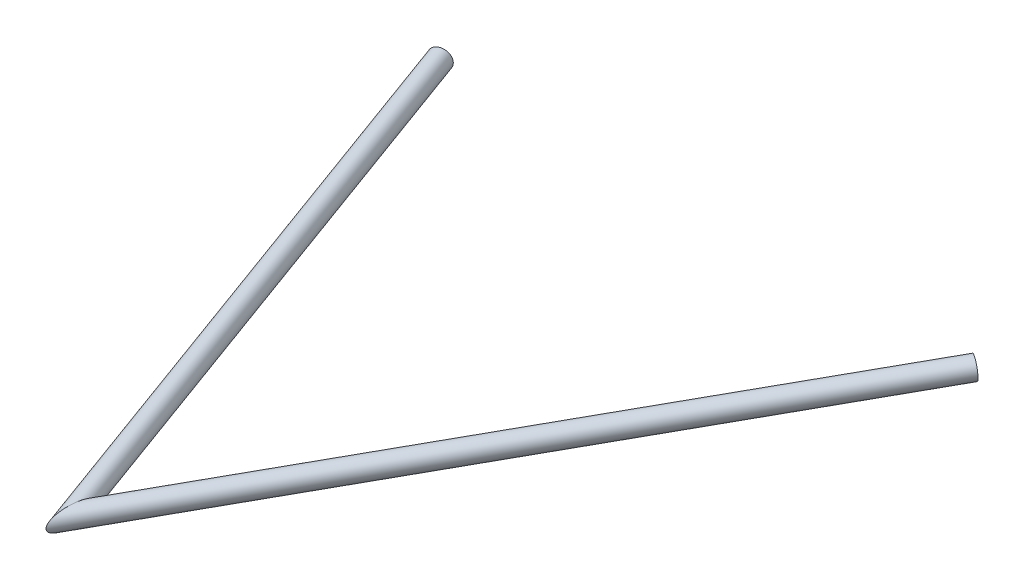
SolidWorks part; units mm, degrees
note: '?' marks a value the reader was unsure of.
material "AISI 4340 Steel, annealed"
ref_plane "Front Plane" through (0, 0, 0) normal (0, 0, 1) x (1, 0, 0)
ref_plane "Top Plane" through (0, 0, 0) normal (0, 1, 0) x (1, 0, 0)
ref_plane "Right Plane" through (0, 0, 0) normal (1, 0, 0) x (0, 0, -1)
sketch3d "reference sketch"
  line L2 (315.5633, 0, -538.6496) -> (-16.5778, -30.7429, -28.3749)
  line L3 (-16.5778, -30.7429, -28.3749) -> (-183.4, 0, -538.6496)
sketch3d "3DSketch2"
  line L0 (315.5633, 0, -538.6496) -> (-16.5778, -30.7429, -28.3749) construction
  line L1 (315.5633, 0, -538.6496) -> (-16.5778, -30.7429, -28.3749)
  line L2 (-16.5778, -30.7429, -28.3749) -> (-183.4, 0, -538.6496) construction
  line L3 (-16.5778, -30.7429, -28.3749) -> (-183.4, 0, -538.6496)
other "Pipe standard s40 PIPE 1 SCH 40(5)" corner treatment miter
ref_plane "Plane1" through (-16.5778, -30.7429, -28.3749) normal (-0.3102, 0.0572, -0.9489) x (-0.8849, 0.3474, 0.3102)
sketch "Sketch1" plane through (-16.5778, -30.7429, -28.3749) normal (-0.3102, 0.0572, -0.9489) x (-0.8849, 0.3474, 0.3102)
  circle A0 centre (0, 0) radius 6.985
  circle A1 centre (0, 0) radius 9.525
  point P3 (0, 0)
  dimension "D1" = 19.05
  dimension "D2" = 2.54
ref_axis "upper pivot axis" through (315.5633, 0, -538.6496) along (-1, 0, 0)?
ref_point "upright mounting point"
